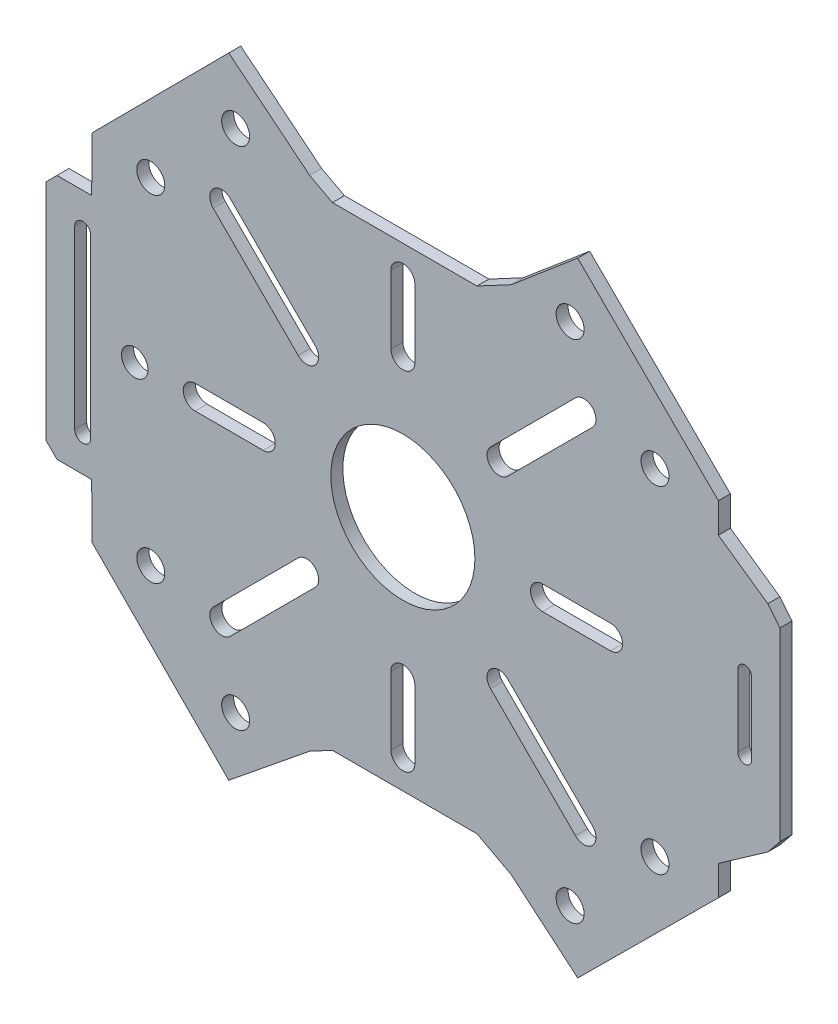
SolidWorks part; units mm, degrees
ref_plane "前视基准面" through (0, 0, 0) normal (0, 0, 1) x (1, 0, 0)
ref_plane "上视基准面" through (0, 0, 0) normal (0, 1, 0) x (1, 0, 0)
ref_plane "右视基准面" through (0, 0, 0) normal (1, 0, 0) x (0, 0, -1)
sketch "Upper_board" plane through (0, 0, 0) normal (0, 0, 1) x (1, 0, 0)
  line L0 (146.4713, -65.3649) -> (146.4713, 899.9684) construction
  line L1 (-20.8934, 31.6066) -> (-31.5, 21) construction
  line L2 (0, 0) -> (0, 48.26) construction
  line L3 (0, 0) -> (79.7901, 0) construction
  line L4 (0, 29.6377) -> (9.2582, 29.6377)
  line L5 (9.2582, 29.6377) -> (13.5301, 31.9144)
  line L6 (13.5301, 31.9144) -> (21.8452, 38.9473)
  line L7 (21.8452, 38.9473) -> (39.4221, 21.4832)
  line L8 (39.4221, 21.4832) -> (39.4221, 17.7594)
  line L9 (39.4221, 17.7594) -> (45.6027, 13.4317)
  line L10 (45.6027, 13.4317) -> (47.1171, 11.5642)
  line L11 (47.1171, 11.5642) -> (47.1171, -11.5642)
  line L12 (45.6027, -13.4317) -> (47.1171, -11.5642)
  line L13 (39.4221, -17.7594) -> (45.6027, -13.4317)
  line L14 (39.4221, -21.4832) -> (39.4221, -17.7594)
  line L15 (21.8452, -38.9473) -> (39.4221, -21.4832)
  line L16 (13.5301, -31.9144) -> (21.8452, -38.9473)
  line L17 (9.2582, -29.6377) -> (13.5301, -31.9144)
  line L18 (0, -29.6377) -> (9.2582, -29.6377)
  line L19 (0, 29.6377) -> (-8.8004, 29.6377)
  line L20 (-8.8004, 29.6377) -> (-11.6488, 31.1557)
  line L21 (-11.6488, 31.1557) -> (-21.7549, 39.351)
  line L22 (-21.7549, 39.351) -> (-38.8505, 22.145)
  line L23 (-38.8505, 22.145) -> (-38.8781, 15.3642)
  line L24 (-38.8781, 15.3642) -> (-43.2196, 15.3642)
  line L25 (-43.2196, 15.3642) -> (-44.5853, 13.9896)
  line L26 (-44.5853, 13.9896) -> (-44.5853, -13.9896)
  line L27 (-8.8004, -29.6377) -> (-11.6488, -31.1557)
  line L28 (0, -29.6377) -> (-8.8004, -29.6377)
  line L29 (-11.6488, -31.1557) -> (-21.7549, -39.351)
  line L30 (-21.7549, -39.351) -> (-38.8505, -22.145)
  line L31 (-38.8505, -22.145) -> (-38.8781, -15.3642)
  line L32 (-38.8781, -15.3642) -> (-43.2196, -15.3642)
  line L33 (-43.2196, -15.3642) -> (-44.5853, -13.9896)
  line L34 (-22.627, 22.627) -> (-12.0212, 12.0212) construction
  line L35 (-21.5663, 23.6876) -> (-10.9606, 13.0819)
  line L36 (-23.6876, 21.5663) -> (-13.0819, 10.9606)
  line L37 (0, 17.4457) -> (0, 25.9457) construction
  line L38 (-1.5, 17.4457) -> (-1.5, 25.9457)
  line L39 (1.5, 17.4457) -> (1.5, 25.9457)
  line L40 (0, -17.4457) -> (0, -25.9457) construction
  line L41 (-1.5, -17.4457) -> (-1.5, -25.9457)
  line L42 (1.5, -17.4457) -> (1.5, -25.9457)
  line L43 (0, 0) -> (-17.3241, 17.3241) construction
  line L44 (-17.4457, 0) -> (-25.9457, 0) construction
  line L45 (-17.4457, 1.5) -> (-25.9457, 1.5)
  line L46 (-17.4457, -1.5) -> (-25.9457, -1.5)
  line L47 (17.4457, 0) -> (25.9457, 0) construction
  line L48 (17.4457, 1.5) -> (25.9457, 1.5)
  line L49 (17.4457, -1.5) -> (25.9457, -1.5)
  line L50 (-22.627, -22.627) -> (-12.0212, -12.0212) construction
  line L51 (-21.5663, -23.6876) -> (-10.9606, -13.0819)
  line L52 (-23.6876, -21.5663) -> (-13.0819, -10.9606)
  line L53 (22.627, 22.627) -> (12.0212, 12.0212) construction
  line L54 (21.5663, 23.6876) -> (10.9606, 13.0819)
  line L55 (23.6876, 21.5663) -> (13.0819, 10.9606)
  line L56 (22.627, -22.627) -> (12.0212, -12.0212) construction
  line L57 (21.5663, -23.6876) -> (10.9606, -13.0819)
  line L58 (23.6876, -21.5663) -> (13.0819, -10.9606)
  line L59 (-40, -11) -> (-40, 11) construction
  line L60 (-41, -11) -> (-41, 11)
  line L61 (-39, -11) -> (-39, 11)
  line L62 (42.7214, -4.5) -> (42.7214, 4.5) construction
  line L63 (41.8554, -4.5) -> (41.8554, 4.5)
  line L64 (43.5874, -4.5) -> (43.5874, 4.5)
  circle A0 centre (0, 0) radius 9
  circle A3 centre (-20.8934, 31.6066) radius 1.75
  circle A4 centre (-31.5, 21) radius 1.75
  circle A5 centre (-33.5, 0) radius 1.65
  circle A6 centre (20.8934, 31.6066) radius 1.75
  circle A7 centre (31.5, 21) radius 1.75
  circle A8 centre (-20.8934, -31.6066) radius 1.75
  circle A9 centre (-31.5, -21) radius 1.75
  circle A10 centre (20.8934, -31.6066) radius 1.75
  circle A11 centre (31.5, -21) radius 1.75
  arc A12 (-21.5663, 23.6876) -> (-23.6876, 21.5663) centre (-22.627, 22.627) ccw
  arc A13 (-13.0819, 10.9606) -> (-10.9606, 13.0819) centre (-12.0212, 12.0212) ccw
  arc A14 (-1.5, 17.4457) -> (1.5, 17.4457) centre (0, 17.4457) ccw
  arc A15 (1.5, 25.9457) -> (-1.5, 25.9457) centre (0, 25.9457) ccw
  arc A16 (-1.5, -17.4457) -> (1.5, -17.4457) centre (0, -17.4457) cw
  arc A17 (1.5, -25.9457) -> (-1.5, -25.9457) centre (0, -25.9457) cw
  arc A18 (-17.4457, 1.5) -> (-17.4457, -1.5) centre (-17.4457, 0) cw
  arc A19 (-25.9457, -1.5) -> (-25.9457, 1.5) centre (-25.9457, 0) cw
  arc A20 (17.4457, 1.5) -> (17.4457, -1.5) centre (17.4457, 0) ccw
  arc A21 (25.9457, -1.5) -> (25.9457, 1.5) centre (25.9457, 0) ccw
  arc A22 (-21.5663, -23.6876) -> (-23.6876, -21.5663) centre (-22.627, -22.627) cw
  arc A23 (-13.0819, -10.9606) -> (-10.9606, -13.0819) centre (-12.0212, -12.0212) cw
  arc A24 (21.5663, 23.6876) -> (23.6876, 21.5663) centre (22.627, 22.627) cw
  arc A25 (13.0819, 10.9606) -> (10.9606, 13.0819) centre (12.0212, 12.0212) cw
  arc A26 (21.5663, -23.6876) -> (23.6876, -21.5663) centre (22.627, -22.627) ccw
  arc A27 (13.0819, -10.9606) -> (10.9606, -13.0819) centre (12.0212, -12.0212) ccw
  arc A28 (-41, -11) -> (-39, -11) centre (-40, -11) ccw
  arc A29 (-39, 11) -> (-41, 11) centre (-40, 11) ccw
  arc A30 (41.8554, -4.5) -> (43.5874, -4.5) centre (42.7214, -4.5) ccw
  arc A31 (43.5874, 4.5) -> (41.8554, 4.5) centre (42.7214, 4.5) ccw
  point P37 (47.1171, 0)
  point P52 (-17.3241, 17.3241)
  point P59 (-44.5853, 0)
  point P66 (0, 21.6957)
  point P78 (0, -21.6957)
  point P84 (-21.6957, 0)
  point P91 (21.6957, 0)
  point P98 (-17.3241, -17.3241)
  point P105 (17.3241, 17.3241)
  point P112 (17.3241, -17.3241)
  point P119 (-40, 0)
  point P124 (42.7214, 0)
  dimension "D1" = 21
  dimension "D2" = 31.5
  dimension "D3" = 3.3
  dimension "D6" = 3.5
  dimension "D9" = 45
  dimension "D11" = 0
  dimension "D12" = 40
  dimension "D4" = 33.5
  dimension "D5" = 15
  dimension "D7" = 29.6377
  dimension "D8" = 47.1171
  dimension "D10" = 24.5
  dimension "D13" = 0
  dimension "D14" = 21
  dimension "D15" = 45
extrude "凸台-拉伸1" add sketch "Upper_board" along normal blind 1.5
